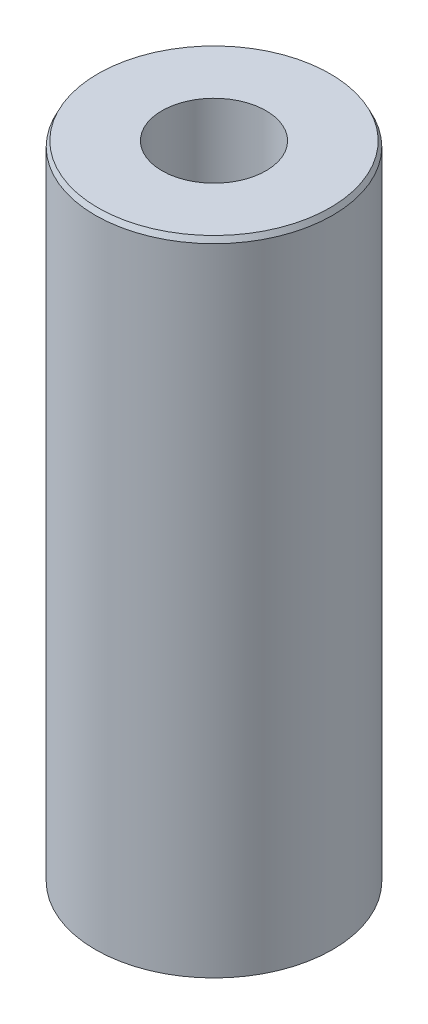
SolidWorks part; units mm, degrees
ref_plane "Front Plane" through (0, 0, 0) normal (0, 0, 1) x (1, 0, 0)
ref_plane "Top Plane" through (0, 0, 0) normal (0, 1, 0) x (1, 0, 0)
ref_plane "Right Plane" through (0, 0, 0) normal (1, 0, 0) x (0, 0, -1)
sketch "Sketch1" plane through (0, 0, 0) normal (0, 1, 0) x (1, 0, 0)
  circle A0 centre (0, 0) radius 52.5
  dimension "SHAFT_OD" = 105
extrude "Boss-Extrude1" add sketch "Sketch1" along normal blind 284.8115
sketch "Sketch2" plane through (0, 0, 0) normal (0, 1, 0) x (1, 0, 0)
  circle A0 centre (0, 0) radius 23.0328
  dimension "BORE_D" = 46.0656
extrude "Cut-Extrude1" cut sketch "Sketch2" along normal through all
chamfer "Chamfer1" distance 2.3339 angle 25.868 2 edges at (0, 284.8115, 52.5) (0, 0, 52.5) first distance on face at (0, 284.8115, 52.5) first distance on face at (0, 0, 23.0328)
